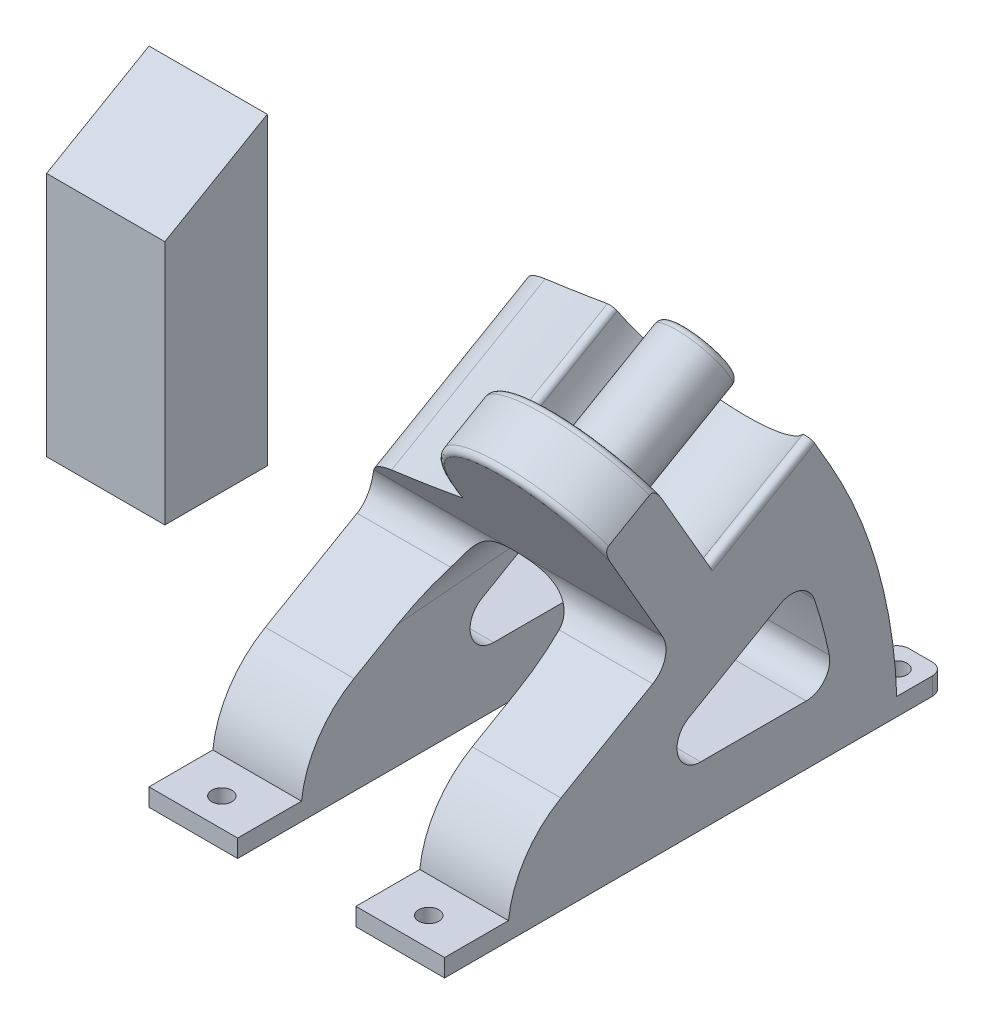
SolidWorks part; units mm, degrees
ref_plane "Ebene vorne" through (0, 0, 0) normal (0, 0, 1) x (1, 0, 0)
ref_plane "Ebene oben" through (0, 0, 0) normal (0, 1, 0) x (1, 0, 0)
ref_plane "Ebene rechts" through (0, 0, 0) normal (1, 0, 0) x (0, 0, -1)
sketch "Skizze1" plane through (0, 0, 0) normal (1, 0, 0) x (0, 0, -1)
  line L0 (0, 0) -> (0, 51.5)
  line L1 (0, 0) -> (-17.3205, 0)
  line L2 (-17.3205, 0) -> (-17.3205, 41.5)
  line L3 (-17.3205, 41.5) -> (0, 51.5)
  line L4 (-8.6603, 0) -> (-8.6603, 46.5) construction
  dimension "D1" = 30
  dimension "D2" = 20
  dimension "D3" = 46.5
extrude "Aufsatz-Linear austragen1" add sketch "Skizze1" along normal blind 20
ref_plane "Ebene1" through (0, 12.875, -22.3002) normal (0, 0.5, -0.866) x (-1, 0, 0)
sketch "Skizze2" plane through (0, 12.875, -22.3002) normal (0, 0.5, -0.866) x (-1, 0, 0)
  line L0 (-20, 44.6003) -> (0, 44.6003) construction
  line L1 (-10, 0) -> (-10, 83.3321) construction
  line L2 (-20, 0) -> (0, 0) construction
  line L3 (90, 62.8984) -> (90, 34.4753)
  line L4 (90, 34.4753) -> (40, 34.4753)
  line L5 (-110, 62.8984) -> (-110, 34.4753)
  line L6 (-60, 41.1677) -> (-60, 34.4753)
  line L7 (40, 41.1677) -> (40, 34.4753)
  line L8 (-60, 34.4753) -> (-110, 34.4753)
  arc A0 (-10, 44.6003) -> (97.1867, 79.9939) centre (-10, 224.6003) ccw construction
  arc A1 (-110, 62.8984) -> (-60, 41.1677) centre (-10, 224.6003) ccw
  arc A2 (40, 41.1677) -> (90, 62.8984) centre (-10, 224.6003) ccw
  point P15 (-10, 22.2829)
  dimension "D1" = 180
  dimension "D3" = 10.125
  dimension "D2" = 200
  dimension "D5" = 100
extrude "Aufsatz-Linear austragen2" add sketch "Skizze2" against normal blind 30
sketch "Skizze4" plane through (-90, 0, 0) normal (-1, 0, 0) x (0, 0, 1)
  line L0 (-5.0625, 42.7315) -> (9.149, 67.3466) construction
  line L1 (-77.0542, 0) -> (77.0542, 0) construction
  line L2 (20.9183, 27.7315) -> (68.9506, 0)
  line L3 (20.9183, 27.7315) -> (-5.0625, 42.7315) construction
  line L4 (20.9183, 27.7315) -> (-5.0625, 42.7315)
  line L5 (-16.5124, 0) -> (-16.5124, 52.2205) construction
  line L6 (-16.5124, 0) -> (68.9506, 0)
  arc A0 (-5.0625, 42.7315) -> (-16.5124, 0) centre (68.9506, 0) ccw
  point P7 (0, 0)
  line M3 (-5.0625, 42.7315) -> (20.9183, 27.7315)
extrude "Aufsatz-Linear austragen3" add sketch "Skizze4" against normal blind 50 contours A0 L6 L2 M3 region at (-90, 14.5784, 14.5432)
sketch "Skizze5" plane through (0, 12.875, -22.3002) normal (0, 0.5, -0.866) x (1, 0, 0)
  line L0 (-79.5999, -56.912) -> (-69.0166, -51.2556) construction
  line L1 (-79.5999, -56.912) -> (-90.1831, -62.5683) construction
  line L2 (-79.5999, -56.912) -> (-87.3609, -42.3907) construction
  line L3 (60, -34.4753) -> (-40, -34.4753) construction
  line L4 (10, -34.4753) -> (10, -101.6812) construction
  arc A0 (-90, -62.8984) -> (-68.8428, -51.5936) centre (-79.5999, -56.912) cw
  arc A1 (-40, -41.1677) -> (-90, -62.8984) centre (10, -224.6003) ccw construction
  circle A2 centre (-67.9368, -41.6076) radius 2.25
  circle A3 centre (-98.8047, -58.1052) radius 2.25
  arc A4 (-40, -41.1677) -> (-90, -62.8984) centre (10, -224.6003) ccw construction
  arc A5 (110, -62.8984) -> (88.8428, -51.5936) centre (99.5999, -56.912) ccw
  arc A6 (-90, -62.8984) -> (-68.8428, -51.5936) centre (-79.5999, -56.912) ccw
  arc A7 (110, -62.8984) -> (88.8428, -51.5936) centre (99.5999, -56.912) cw
  dimension "D1" = 12
  dimension "D5" = 4.5
  dimension "D2" = 0.38
  dimension "D3" = 35
  dimension "D4" = 8
extrude "Schnitt-Linear austragen1" cut sketch "Skizze5" against normal through all contours A7 A5 region at (99.5999, 62.1622, 6.1558)
sketch "Skizze7" plane through (60, 0, 0) normal (1, 0, 0) x (0, 0, -1)
  line L0 (5.0625, 42.7315) -> (-68.9506, 0)
  line L1 (-68.9506, 0) -> (16.5124, 0)
  arc A0 (5.0625, 42.7315) -> (16.5124, 0) centre (-68.9506, 0) cw
  arc A2 (16.5124, 0) -> (5.0625, 42.7315) centre (-68.9506, 0) ccw construction
  point P10 (0, 0)
extrude "Aufsatz-Linear austragen5" add sketch "Skizze7" along normal up to vertex (50 mm away) up to point (110, 42.7315, -5.0625)
ref_plane "Ebene5" [suppressed] through (10, 0, 0) normal (1, 0, 0) x (0, 0, -1)
sketch "Skizze9" [suppressed] plane through (0, 38.6015, -32.3905) normal (0, 0.766, -0.6428) x (1, 0, 0)
  line L0 (-55, -32.1579) -> (-55, -43.6141)
  line L1 (-40, -32.1579) -> (-90, -32.1579) construction
  line L2 (-40, -38.8503) -> (-40, -32.1579) construction
  line L6 (-90, -32.1579) -> (-90, -60.5809)
  line L7 (-40, -38.8503) -> (-40, -32.1579)
  line L8 (-40, -32.1579) -> (-90, -32.1579)
  line L9 (-90, -32.1579) -> (-90, -60.5809)
  line L11 (-55, -32.1579) -> (-90, -32.1579)
  arc A0 (-40, -38.8503) -> (-90, -60.5809) centre (10, -222.2829) ccw construction
  arc A5 (-40, -38.8503) -> (-90, -60.5809) centre (10, -222.2829) ccw
  arc A8 (-55, -43.6141) -> (-90, -60.5809) centre (10, -222.2829) ccw
  dimension "D1" = 15
  dimension "D2" = 0
sketch "Skizze11" [suppressed] plane through (0, 23.2807, -19.5348) normal (0, -0.766, 0.6428) x (1, 0, 0)
  line L0 (60, 32.1579) -> (110, 32.1579)
  line L1 (110, 32.1579) -> (141.0282, 65.9)
  line L2 (141.0282, 65.9) -> (38.3436, 62.9928)
  line L3 (38.3436, 62.9928) -> (60, 32.1579)
  line L4 (-90, 32.1579) -> (-40, 32.1579)
  line L5 (-40, 32.1579) -> (-27.2753, 44.0032)
  line L6 (-27.2753, 44.0032) -> (-71.113, 77.6284)
  line L7 (-71.113, 77.6284) -> (-115.715, 75.5442)
  line L8 (-115.715, 75.5442) -> (-104.047, 34.6918)
  line L9 (-104.047, 34.6918) -> (-90, 32.1579)
ref_plane "Ebene6" through (0, 1.462, -16.7109) normal (0, 0.0872, -0.9962) x (-1, 0, 0)
sketch "Skizze12" plane through (0, 1.462, -16.7109) normal (0, 0.0872, -0.9962) x (-1, 0, 0)
  line L0 (75, -1.4391) -> (75, 33.5609)
  line L1 (40, -1.4391) -> (90, -1.4391) construction
  line L2 (75, 33.5609) -> (55, 33.5609)
  line L3 (55, 33.5609) -> (55, -1.4391)
  line L4 (55, -1.4391) -> (75, -1.4391)
  line L5 (40, 42.1277) -> (40, -1.4391) construction
  line L6 (90, -1.4391) -> (90, 42.1277) construction
  line L7 (40, -1.4391) -> (-60, -1.4391) construction
  line L8 (-10, -1.4391) -> (-10, 52.6156) construction
  line L9 (-75, -1.4391) -> (-95, -1.4391)
  line L10 (-75, 33.5609) -> (-75, -1.4391)
  line L11 (-95, -1.4391) -> (-95, 33.5609)
  line L12 (-95, 33.5609) -> (-75, 33.5609)
  dimension "D1" = 15
  dimension "D2" = 15
  dimension "D3" = 35
extrude "Schnitt-Linear austragen4" cut sketch "Skizze12" against normal through all
fillet "Verrundung5" radius 10 2 edges at (75, 33.079, 6.9731) (95, 33.079, 6.9731) tangent propagation no
fillet "Verrundung6" radius 10 2 edges at (-55, 33.079, 6.9731) (-75, 33.079, 6.9731)
sketch "Skizze13" plane through (0, 0, 0) normal (0, 1, 0) x (1, 0, 0)
  line L0 (-40, 16.5124) -> (-40, 24.5124)
  line L1 (-40, 24.5124) -> (-48, 24.5124)
  line L2 (-44, 20.5124) -> (-44, 16.5124) construction
  line L3 (-51.9152, 20.5124) -> (-40, 20.5124) construction
  line L4 (-40, 16.5124) -> (-55, 16.5124) construction
  line L5 (-48, 16.5124) -> (-48, 24.5124)
  line L6 (-55, 16.5124) -> (-75, 16.5124) construction
  line L7 (-65, 16.5124) -> (-65, 48.5338) construction
  line L8 (60, 16.5124) -> (-40, 16.5124) construction
  line L9 (10, 16.5124) -> (10, 91.6227) construction
  line L10 (-40, 16.5124) -> (-40, 14.7882)
  line L11 (-40, 16.5124) -> (-40, -68.9506) construction
  line L12 (-40, 14.7882) -> (-48, 14.7882)
  line L13 (-48, 14.7882) -> (-48, 16.5124)
  line L14 (-90, 24.5124) -> (-82, 24.5124)
  line L15 (-90, 16.5124) -> (-90, 24.5124)
  line L16 (-82, 16.5124) -> (-82, 24.5124)
  line L17 (-82, 14.7882) -> (-82, 16.5124)
  line L18 (-90, 16.5124) -> (-90, 14.7882)
  line L19 (-90, 14.7882) -> (-82, 14.7882)
  line L20 (71.9152, 20.5124) -> (60, 20.5124) construction
  line L21 (64, 20.5124) -> (64, 16.5124) construction
  line L22 (68, 14.7882) -> (68, 16.5124)
  line L23 (60, 14.7882) -> (68, 14.7882)
  line L24 (60, 16.5124) -> (60, 14.7882)
  line L25 (68, 16.5124) -> (68, 24.5124)
  line L26 (60, 24.5124) -> (68, 24.5124)
  line L27 (60, 16.5124) -> (60, 24.5124)
  line L28 (110, 14.7882) -> (102, 14.7882)
  line L29 (110, 16.5124) -> (110, 14.7882)
  line L30 (102, 14.7882) -> (102, 16.5124)
  line L31 (102, 16.5124) -> (102, 24.5124)
  line L32 (110, 16.5124) -> (110, 24.5124)
  line L33 (110, 24.5124) -> (102, 24.5124)
  circle A0 centre (-44, 20.5124) radius 1.7
  circle A1 centre (-86, 20.5124) radius 1.7
  circle A2 centre (64, 20.5124) radius 1.7
  circle A3 centre (106, 20.5124) radius 1.7
  dimension "D1" = 3.4
  dimension "D2" = 4
extrude "Aufsatz-Linear austragen9" add sketch "Skizze13" along normal blind 3
fillet "Verrundung7" radius 2 4 edges at (-40, 1.5, -24.5124) (-48, 1.5, -24.5124) (-82, 1.5, -24.5124) (-90, 1.5, -24.5124)
ref_plane "Ebene7" through (0, 3, 0) normal (0, -1, 0) x (-1, 0, 0)
sketch "Skizze14" plane through (0, 3, 0) normal (0, -1, 0) x (-1, 0, 0)
  line L0 (90, -49.2106) -> (75, -49.2106)
  line L1 (90, -20.9183) -> (90, -68.9506) construction
  line L2 (75, -68.9506) -> (75, -32.9844) construction
  line L3 (75, -49.2106) -> (75, -68.9506)
  line L4 (75, -68.9506) -> (90, -68.9506)
  line L5 (90, -68.9506) -> (90, -49.2106)
  line L6 (75, -68.9506) -> (55, -68.9506) construction
  line L7 (65, -68.9506) -> (65, -28.0183) construction
  line L8 (40, -68.9506) -> (-60, -68.9506) construction
  line L9 (-10, -68.9506) -> (-10, -6.4616) construction
  line L10 (40, -68.9506) -> (40, -49.2106)
  line L11 (55, -68.9506) -> (40, -68.9506)
  line L12 (55, -49.2106) -> (55, -68.9506)
  line L13 (40, -49.2106) -> (55, -49.2106)
  line L14 (-60, -49.2106) -> (-75, -49.2106)
  line L15 (-75, -49.2106) -> (-75, -68.9506)
  line L16 (-75, -68.9506) -> (-60, -68.9506)
  line L17 (-60, -68.9506) -> (-60, -49.2106)
  line L18 (-110, -68.9506) -> (-110, -49.2106)
  line L19 (-95, -68.9506) -> (-110, -68.9506)
  line L20 (-95, -49.2106) -> (-95, -68.9506)
  line L21 (-110, -49.2106) -> (-95, -49.2106)
  dimension "D1" = 19.74
extrude "Schnitt-Linear austragen5" cut sketch "Skizze14" against normal through all
fillet "Verrundung9" radius 18 2 edges at (-47.5, 11.3969, 49.2106) (-82.5, 11.3969, 49.2106)
sketch "Skizze30" plane through (0, 3, 0) normal (0, 1, 0) x (1, 0, 0)
  line L0 (60, -63.7545) -> (75, -63.7545)
  line L1 (75, -63.7545) -> (75, -68.7545)
  line L2 (75, -68.7545) -> (60, -68.7545)
  line L3 (60, -68.7545) -> (60, -63.7545)
  line L4 (95, -63.7545) -> (110, -63.7545)
  line L5 (110, -63.7545) -> (110, -68.7545)
  line L6 (110, -68.7545) -> (95, -68.7545)
  line L7 (95, -68.7545) -> (95, -63.7545)
  dimension "D1" = 5
extrude "Aufsatz-Linear austragen15" add sketch "Skizze30" against normal up to vertex up to point (75, 0, 68.9506)
sketch "Skizze15" plane through (0, 3, 0) normal (0, -1, 0) x (-1, 0, 0)
  line L0 (90, -56.4825) -> (75, -56.4825) construction
  line L1 (90, -63.7545) -> (90, -49.2106) construction
  line L2 (75, -49.2106) -> (75, -63.7545) construction
  line L3 (75, -68.9506) -> (55, -68.9506) construction
  line L4 (65, -68.9506) -> (65, -29.984) construction
  line L5 (40, -68.9506) -> (-60, -68.9506) construction
  line L6 (-10, -68.9506) -> (-10, -7.0981) construction
  line L7 (82.5, -35.3047) -> (82.5, -63.7545) construction
  line L9 (75, -63.7545) -> (90, -63.7545) construction
  line L10 (-60, -68.7545) -> (-60, -49.2106) construction
  line L11 (-60, -49.2106) -> (-75, -49.2106) construction
  circle A0 centre (82.5, -55.1906) radius 1.7
  circle A1 centre (47.5, -55.1906) radius 1.7
  circle A2 centre (-102.5, -55.1906) radius 1.7
  circle A3 centre (-67.5, -55.1906) radius 1.7
  dimension "D1" = 3.4
  dimension "D2" = 5.98
extrude "Schnitt-Linear austragen6" cut sketch "Skizze15" along normal through all
ref_plane "Ebene8" through (0, 12.875, -22.3002) normal (0, 0.5, -0.866) x (1, 0, 0)
sketch "Skizze18" plane through (0, 12.875, -22.3002) normal (0, 0.5, -0.866) x (1, 0, 0)
  line L0 (60, -25.4892) -> (-40, -25.4892) construction
  line L1 (60, 5.6318) -> (60, -34.4753) construction
  line L2 (-40, -34.4753) -> (-40, 5.6318) construction
  line L3 (10, -25.4892) -> (10, 9.2287) construction
  line L4 (-50, -24.4753) -> (70, -24.4753)
  line L5 (-50, -24.4753) -> (-50, -14.2753)
  line L6 (-50, -14.2753) -> (70, -14.2753)
  line L7 (70, -24.4753) -> (70, -14.2753)
  line L9 (110, -34.4753) -> (60, -34.4753) construction
  point P13 (10, -14.2753)
  point P14 (10, -24.4753)
  dimension "D1" = 10.2
  dimension "D2" = 120
  dimension "D3" = 10
extrude "Schnitt-Linear austragen8" cut sketch "Skizze18" against normal blind 10
fillet "Verrundung12" radius 18 2 edges at (102.5, 11.3969, 49.2106) (67.5, 11.3969, 49.2106)
fillet "Verrundung13" radius 2 1 edges at (-40, 41.0273, 11.2741)
sketch "Skizze16" plane through (-40, 0, 0) normal (1, 0, 0) x (0, 0, -1)
  circle A0 centre (7.4883, 22.2505) radius 102.0124
extrude "Schnitt-Linear austragen7" cut sketch "Skizze16" against normal through all
sketch "Skizze19" plane through (60, 0, 0) normal (-1, 0, 0) x (0, 0, 1)
  line L0 (-8.2475, 3.755) -> (-8.2475, 34.755) construction
  circle A0 centre (-8.2475, 34.755) radius 1.5
  circle A1 centre (-8.2475, 3.755) radius 1.5
  point P4 (-6.5499, 3.4354)
  point P5 (-8.2475, 3.755)
  dimension "D2" = 3
  dimension "D3" = 3
  dimension "D1" = 31
extrude "Schnitt-Linear austragen9" [suppressed] cut sketch "Skizze19" against normal blind 10 contours A1
sketch "Skizze20" [suppressed] plane through (60, 0, 0) normal (-1, 0, 0) x (0, 0, 1)
  line L0 (-5.7475, 3.755) -> (-5.7475, 0) construction
  line L1 (68.9506, 0) -> (-24.5124, 0) construction
  line L2 (-5.7475, 0) -> (-10.7475, 0)
  line L3 (-10.7475, 3.755) -> (-10.7475, 0) construction
  line L4 (-5.7475, 0) -> (-4.4475, 0)
  line L5 (-4.4475, 0) -> (-4.4475, 7.5101)
  line L6 (-8.2475, 3.755) -> (-8.2475, -0.8247) construction
  line L7 (-12.0475, 0) -> (-12.0475, 7.5101)
  line L8 (-10.7475, 0) -> (-12.0475, 0)
  line L9 (-8.2475, 3.755) -> (-21.2712, 3.755) construction
  line L10 (-5.7475, 7.5101) -> (-4.4475, 7.5101)
  line L11 (-5.7475, 7.5101) -> (-10.7475, 7.5101)
  line L12 (-10.7475, 7.5101) -> (-12.0475, 7.5101)
  line L13 (-5.7475, 34.755) -> (-5.7475, 29.4363) construction
  line L14 (-7.6633, 33.1471) -> (-4.4475, 33.1471)
  line L15 (-7.6633, 33.1471) -> (-7.6633, 36.363)
  line L16 (-7.6633, 36.363) -> (-4.4475, 36.363)
  line L17 (-4.4475, 33.1471) -> (-4.4475, 36.363)
  line L18 (-7.6633, 33.1471) -> (-4.4475, 36.363) construction
  line L19 (-7.6633, 36.363) -> (-4.4475, 33.1471) construction
  circle A0 centre (-8.2475, 3.755) radius 1.5
  circle A1 centre (-8.2475, 3.755) radius 1.5 construction
  circle A2 centre (-8.2475, 3.755) radius 2.5
  circle A3 centre (-6.0554, 34.755) radius 0.3079 construction
  arc A4 (-8.3906, 36.363) -> (-7.6633, 37.8711) centre (68.9506, 0) ccw
  arc A5 (-13.0654, 24.027) -> (-16.4597, 3) centre (68.9506, 0) ccw construction
  point P19 (-4.4475, 3.755)
  point P22 (-12.0475, 3.755)
  circle M11 centre (-8.2475, 3.755) radius 1.5
  line M25 (-24.5124, 0) -> (68.9506, 0)
  dimension "D1" = 5
  dimension "D3" = 1.3
  dimension "D2" = 1.3
extrude "Aufsatz-Linear austragen11" [suppressed] add sketch "Skizze20" along normal blind 2 contours A2 M11 | L11 L12 L7 L5 L10 A2 M25
chamfer "Fase1" [suppressed] distance 2 angle 45
ref_plane "Ebene9" through (0, 5.4241, -18.5152) normal (0, 0.2811, -0.9597) x (-1, 0, 0)
sketch "Skizze21" plane through (0, 5.4241, -18.5152) normal (0, 0.2811, -0.9597) x (-1, 0, 0)
  line L0 (-60, 8.8181) -> (-75, 8.8181) construction
  line L1 (-60, -1.7485) -> (-60, 19.3847) construction
  line L2 (-75, 20.1646) -> (-75, 22.6306) construction
  circle A0 centre (-67.5, 8.8181) radius 1.5
  dimension "D1" = 3
extrude "Schnitt-Linear austragen12" [suppressed] cut sketch "Skizze21" against normal blind 10
ref_plane "Ebene10" through (0, 0.5811, -16.5447) normal (0, 0.0351, -0.9994) x (-1, 0, 0)
sketch "Skizze22" plane through (0, 0.5811, -16.5447) normal (0, 0.0351, -0.9994) x (-1, 0, 0)
  line L0 (-60, 6.4204) -> (-75, 6.4204) construction
  line L2 (-75, 24.3084) -> (-75, -0.5796) construction
  line L3 (-60, 2.4204) -> (-68, 2.4204) construction
  circle A0 centre (-67.5, 6.4204) radius 1.5
  dimension "D1" = 3
  dimension "D2" = 4
extrude "Schnitt-Linear austragen13" cut sketch "Skizze22" against normal blind 10
sketch "Skizze23" plane through (0, 12.875, -22.3002) normal (0, 0.5, -0.866) x (1, 0, 0)
  line L0 (110, -34.4753) -> (110, -66.7784) construction
  circle A1 centre (99.5999, -56.912) radius 10.125 construction
  circle A3 centre (10, -224.6003) radius 180 construction
  circle A4 centre (96, -50.7038) radius 14
  dimension "D1" = 28
  dimension "D2" = 20.25
  dimension "D3" = 360
sketch "Skizze24" plane through (0, 12.875, -22.3002) normal (0, 0.5, -0.866) x (1, 0, 0)
  line L1 (110, -34.4753) -> (60, -34.4753) construction
  line L2 (110, -42.4963) -> (114.8778, -55.8766)
  line L3 (114.8778, -55.8766) -> (84.4554, -65.8041)
  line L4 (84.4554, -65.8041) -> (80.026, -47.841)
  line L5 (110, -34.4753) -> (110, -66.7784) construction
  arc A0 (110, -42.4963) -> (80.026, -47.841) centre (96, -50.7038) ccw
  arc A1 (88.8428, -51.5936) -> (60, -41.1677) centre (10, -224.6003) ccw construction
extrude "Schnitt-Linear austragen14" cut sketch "Skizze24" against normal blind 20
sketch "Skizze27" plane through (0, 2.875, -4.9796) normal (0, 0.5, -0.866) x (1, 0, 0)
  line L0 (110, -34.4753) -> (110, -66.7784) construction
  line L1 (110, -58.9113) -> (110, -54.7351)
  line L2 (110, -54.7351) -> (110, -43.0057)
  line L3 (110, -43.0057) -> (94.9412, -37.0285)
  line L4 (94.9412, -37.0285) -> (80.026, -47.841)
  line L5 (110, -42.4963) -> (110, -50.9256) construction
  arc A0 (80.026, -47.841) -> (110, -58.9113) centre (96, -50.7038) ccw
extrude "Aufsatz-Linear austragen13" add sketch "Skizze27" against normal up to surface (10 mm away) up to face at (85.4816, 32.0629, 23.419)
sketch "Skizze26" plane through (0, 2.875, -4.9796) normal (0, 0.5, -0.866) x (1, 0, 0)
  circle A0 centre (96, -50.7038) radius 5.9
  dimension "D1" = 11.8
extrude "Aufsatz-Linear austragen14" add sketch "Skizze26" along normal blind 20
fillet "Verrundung14" radius 4.5 2 edges at (68.4587, 27.7315, 20.9183) (101.5413, 27.7315, 20.9183)
fillet "Verrundung15" radius 1 1 edges at (96, 61.8953, 6.0017)
sketch "Skizze28" plane through (110, 0, 0) normal (1, 0, 0) x (0, 0, -1)
  line L0 (5.8469, 10) -> (-31.6301, 10)
  line L1 (-68.9506, 0) -> (24.5124, 0) construction
  line L2 (-31.6301, 10) -> (0.8259, 28.7385)
  line L3 (-24.8154, 25.4815) -> (-40.3293, 16.5245) construction
  arc A0 (5.8469, 10) -> (0.8259, 28.7385) centre (-68.9506, 0) ccw
  arc A1 (16.4597, 3) -> (5.0625, 42.7315) centre (-68.9506, 0) ccw construction
  dimension "D1" = 10
  dimension "D2" = 10
  dimension "D3" = 10
extrude "Schnitt-Linear austragen15" cut sketch "Skizze28" against normal through all
fillet "Verrundung16" radius 4 6 edges at (102.5, 10, 31.6301) (67.5, 10, 31.6301) (102.5, 10, -5.8469) (67.5, 10, -5.8469) (101.8312, 28.7385, -0.8259) (68.1688, 28.7385, -0.8259)
fillet "Verrundung17" radius 8.8 1 edges at (60, 41.0273, 11.2741)
fillet "Verrundung18" radius 1 2 edges at (90.3775, 59.9696, 27.9839) (90.3775, 54.9696, 36.6442)
fillet "Verrundung19" radius 1 2 edges at (110, 44.6778, 7.6082) (80.026, 49.3065, 10.2806)
fillet "Verrundung20" radius 2 8 edges at (110, 1.5566, 68.7545) (95, 1.5566, 68.7545) (75, 1.5566, 68.7545) (60, 1.5566, 68.7545) (60, 1.5, -24.5124) (68, 1.5, -24.5124) (102, 1.5, -24.5124) (110, 1.5, -24.5124)
sketch "Skizze31" plane through (0, 3, 0) normal (0, 1, 0) x (1, 0, 0)
  line L0 (60, -60.0106) -> (110, -60.0106)
  line L1 (60, -66.7545) -> (60, -49.2106) construction
  line L3 (60, -49.2106) -> (75, -49.2106) construction
  line L4 (110, -49.2106) -> (110, -66.7545) construction
  line L7 (110, -60.0106) -> (122.4657, -77.509)
  line L8 (122.4657, -77.509) -> (79.9978, -80.1771)
  line L9 (79.9978, -80.1771) -> (48.4247, -75.7302)
  line L10 (48.4247, -75.7302) -> (60, -60.0106)
  dimension "D1" = 10.8
extrude "Schnitt-Linear austragen16" cut sketch "Skizze31" against normal blind 10
